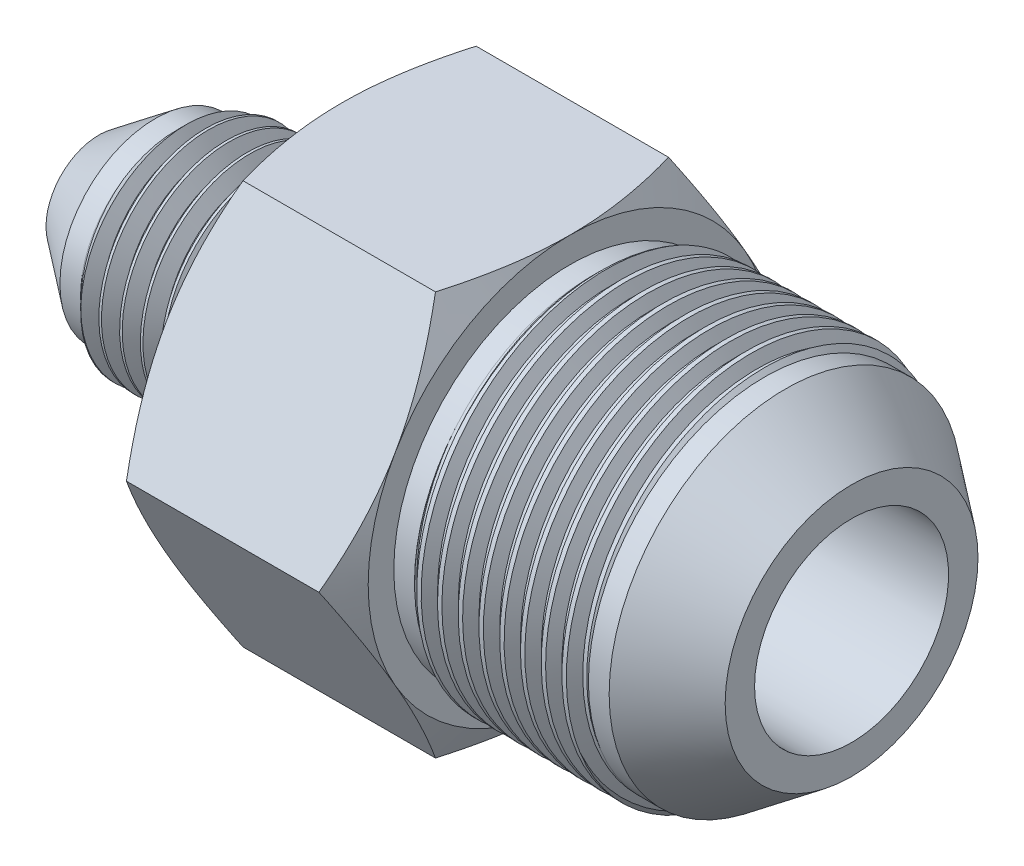
SolidWorks part; units mm, degrees
ref_plane "Front" through (0, 0, 0) normal (0, 0, 1) x (1, 0, 0)
ref_plane "Top" through (0, 0, 0) normal (0, 1, 0) x (1, 0, 0)
ref_plane "Right" through (0, 0, 0) normal (1, 0, 0) x (0, 0, -1)
sketch "Sketch1" plane through (0, 0, 0) normal (0, 0, 1) x (1, 0, 0)
  line L0 (-19.2, 5.5562) -> (-19.2, -5.5562) construction
  line L1 (19.2, 9.525) -> (19.2, -9.525) construction
  line L2 (-19.2, 0) -> (19.2, 0)
  line L4 (-19.2, 0) -> (-19.2, 5.5562)
  line L5 (4.8375, 9.525) -> (19.2, 9.525)
  line L6 (19.2, 0) -> (19.2, 9.525)
  line L7 (-19.2, 2.2) -> (-19.2, -2.2) construction
  line L8 (-6.8219, 6.3182) -> (-6.8219, -6.3182) construction
  line L9 (4.8375, 6.3182) -> (4.8375, -6.3182) construction
  line L10 (19.2, 4.95) -> (19.2, -4.95)
  point P4 (4.8375, 0)
  point P20 (19.2, 0)
  dimension "Thread Diameter 1" = 19.05
  dimension "Length" = 38.4
  dimension "L1" = 14.3625
  dimension "Thread Diameter 2" = 11.1125
  dimension "ID2" = 4.4
  dimension "D2" = 12.6365
  dimension "L2" = 12.3781
  dimension "ID1" = 9.9
sketch "Sketch2" plane through (0, 0, 0) normal (1, 0, 0) x (0, 0, -1)
  line L1 (-5.9467, 10.3) -> (-11.8934, 0) construction
  line L2 (-11.8934, 0) -> (-5.9467, -10.3) construction
  line L3 (-5.9467, -10.3) -> (5.9467, -10.3) construction
  line L4 (5.9467, -10.3) -> (11.8934, 0) construction
  line L5 (11.8934, 0) -> (5.9467, 10.3) construction
  line L6 (5.9467, 10.3) -> (-5.9467, 10.3) construction
  circle A0 centre (0, 0) radius 6.35 construction
  circle A1 centre (0, 0) radius 10.3 construction
  circle A2 centre (0, 0) radius 3.175 construction
  dimension "For Tube OD 1" = 12.7
  dimension "For Tube OD 2" = 6.35
  dimension "Hex" = 20.6
sketch "Sketch3" plane through (0, 0, 0) normal (0, 0, 1) x (1, 0, 0)
  line L0 (6.4272, 9.525) -> (4.8375, 9.525)
  line L2 (4.8375, 8.9937) -> (4.8375, 9.525)
  line L7 (19.2, 9.525) -> (14.2348, 9.525)
  line L8 (-8.5676, 5.5563) -> (-7.8802, 4.8688)
  line L10 (19.2, 0) -> (19.2, 9.525)
  line L12 (4.8375, 9.525) -> (19.2, 9.525)
  line L16 (14.2348, 9.525) -> (14.7661, 8.9937)
  line L17 (4.8375, 9.525) -> (4.8375, 10.3)
  line L18 (-14.5761, 5.5562) -> (-8.5676, 5.5563)
  line L19 (4.8375, 10.3) -> (-6.8219, 10.3)
  line L20 (-6.8219, 10.3) -> (-6.8219, 5.5562)
  line L21 (14.7661, 8.9937) -> (15.8244, 8.9937)
  line L22 (-7.8802, 4.8688) -> (-6.8219, 4.8688)
  line L24 (-19.1339, 5.6708) -> (-19.663, 4.7543)
  line L25 (-19.663, 4.7543) -> (-20.1922, 5.6708)
  line L26 (-20.1922, 5.6708) -> (-19.1339, 5.6708)
  line L27 (-19.663, 4.7543) -> (-19.663, 4.8688)
  line L28 (-19.663, 5.6708) -> (-19.663, 5.5562)
  line L29 (-19.5969, 4.8688) -> (-19.7292, 4.8688)
  line L30 (-19.2, 5.5562) -> (-20.126, 5.5562)
  line L31 (-19.1669, 5.6135) -> (-20.1591, 5.6135)
  line L32 (-6.8219, 4.8688) -> (-6.8219, 5.5562)
  line L33 (20.1471, 9.7176) -> (19.618, 8.8011)
  line L34 (19.618, 8.8011) -> (19.0888, 9.7176)
  line L35 (19.0888, 9.7176) -> (20.1471, 9.7176)
  line L36 (19.618, 8.8011) -> (19.618, 8.9937)
  line L37 (19.618, 9.7176) -> (19.618, 9.525)
  line L38 (19.7292, 8.9937) -> (19.5068, 8.9937)
  line L39 (20.0359, 9.525) -> (19.2, 9.525)
  line L40 (20.0915, 9.6213) -> (19.1444, 9.6213)
  line L41 (15.8244, 8.9937) -> (19.2, 6.45)
  line L42 (19.2, 6.45) -> (19.2, 9.525)
  line L43 (5.8958, 8.9937) -> (4.8375, 8.9937)
  line L44 (6.4272, 9.525) -> (5.8958, 8.9937)
  line L45 (19.2, 0) -> (19.2, 9.525) construction
  line L46 (0, -10.3) -> (0, 10.3) construction
  line L47 (-19.2, 2.7) -> (-16.3218, 4.8688)
  line L48 (-19.2, 0) -> (-19.2, 5.5562) construction
  line L49 (-16.3218, 4.8688) -> (-15.2635, 4.8688)
  line L50 (-15.2635, 4.8688) -> (-14.5761, 5.5562)
  line L51 (19.2, 0) -> (4.8375, 0)
  line L52 (4.8375, 0) -> (-6.8219, 0)
  line L53 (-6.8219, 6.3182) -> (-6.8219, -6.3182) construction
  line L54 (-6.8219, 0) -> (-19.2, 0)
  line L55 (-19.2, 5.5562) -> (-19.2, -5.5562) construction
  line L56 (-19.2, 0) -> (-19.2, 2.7)
  point P14 (-19.2, 5.5562)
  point P43 (-19.663, 4.8688)
  point P46 (-19.663, 5.5562)
  point P49 (-19.663, 5.6135)
  point P57 (19.618, 8.9937)
  point P59 (19.618, 9.525)
  point P63 (19.618, 9.6213)
  point P86 (0, 10.3)
  dimension "Pitch2" = 1.0583
  dimension "D3" = 0.1323
  dimension "Pitch1" = 1.0583
  dimension "D4" = 0.2224
  dimension "Flare Angle" = 37
  dimension "D6" = 45
  dimension "Flare Angle 2" = 37
  dimension "D1" = 45
  dimension "Thread Length 1" = 13.3042
  dimension "Thread Length 2" = 11.3198
  dimension "D5" = 1.5
sketch "Sketch6" plane through (0, 0, 0) normal (0, 0, 1) x (1, 0, 0)
  line L0 (14.2348, 9.525) -> (14.7661, 8.9937) construction
  line L2 (14.7661, 8.9937) -> (15.8244, 8.9937) construction
  line L7 (15.8244, 8.9937) -> (19.2, 6.45) construction
  line L16 (-19.2, 0) -> (19.2, 0) construction
  line L21 (14.2348, 9.525) -> (14.7661, 8.9937)
  line L25 (14.7661, 8.9937) -> (15.8244, 8.9937)
  line L26 (15.8244, 8.9937) -> (19.2, 6.45)
  line L27 (-19.2, 0) -> (19.2, 0)
  line L28 (4.8375, 6.3182) -> (4.8375, -6.3182) construction
  line L29 (4.8375, 10.3) -> (-6.8219, 10.3) construction
  line L30 (-6.8219, 6.3182) -> (-6.8219, -6.3182) construction
  line L31 (-19.2, 2.7) -> (-16.3218, 4.8688) construction
  line L32 (-16.3218, 4.8688) -> (-15.2635, 4.8688) construction
  line L33 (-15.2635, 4.8688) -> (-14.5761, 5.5562) construction
  line L34 (-14.5761, 5.5562) -> (-8.5676, 5.5563) construction
  line L35 (-8.5676, 5.5563) -> (-7.8802, 4.8688) construction
  line L36 (-7.8802, 4.8688) -> (-6.8219, 4.8688) construction
  line L37 (5.8958, 8.9937) -> (4.8375, 8.9937) construction
  line L38 (6.4272, 9.525) -> (5.8958, 8.9937) construction
  line L39 (4.8375, 10.3) -> (4.8375, 8.9937)
  line L40 (4.8375, 10.3) -> (-6.8219, 10.3)
  line L41 (-6.8219, 10.3) -> (-6.8219, 4.8688)
  line L42 (-19.2, 2.7) -> (-16.3218, 4.8688)
  line L43 (-16.3218, 4.8688) -> (-15.2635, 4.8688)
  line L44 (-15.2635, 4.8688) -> (-14.5761, 5.5562)
  line L45 (-14.5761, 5.5562) -> (-8.5676, 5.5563)
  line L46 (-8.5676, 5.5563) -> (-7.8802, 4.8688)
  line L47 (-7.8802, 4.8688) -> (-6.8219, 4.8688)
  line L48 (5.8958, 8.9937) -> (4.8375, 8.9937)
  line L49 (6.4272, 9.525) -> (5.8958, 8.9937)
  line L50 (19.2, 6.45) -> (19.2, 0)
  line L51 (14.2348, 9.525) -> (6.4272, 9.525)
  line L52 (-19.2, 2.7) -> (-19.2, 0)
revolve "Revolve3" add sketch "Sketch6" angle 360 about L27
sketch "Sketch14" plane through (19.2, 0, 0) normal (-1, 0, 0) x (0, 0, 1)
  circle A2 centre (0, 0) radius 9.525
sketch "Sketch15" plane through (0, 0, 0) normal (0, 0, 1) x (1, 0, 0)
  line L1 (20.0915, 9.6213) -> (19.7292, 8.9937)
  line L2 (19.7292, 8.9937) -> (19.5068, 8.9937)
  line L3 (19.5068, 8.9937) -> (19.1444, 9.6213)
  line L4 (19.1444, 9.6213) -> (20.0915, 9.6213)
ref_plane "Plane1" through (-6.8219, 0, 0) normal (1, 0, 0) x (0, 0, -1)
sketch "Sketch12" plane through (-6.8219, 0, 0) normal (1, 0, 0) x (0, 0, -1)
  line L0 (5.9467, 10.3) -> (-5.9467, 10.3) construction
  line L1 (-5.9467, 10.3) -> (-11.8934, 0) construction
  line L2 (-11.8934, 0) -> (-5.9467, -10.3) construction
  line L3 (-5.9467, -10.3) -> (5.9467, -10.3) construction
  line L4 (5.9467, -10.3) -> (11.8934, 0) construction
  line L5 (11.8934, 0) -> (5.9467, 10.3) construction
  line L7 (5.9467, 10.3) -> (-5.9467, 10.3)
  line L8 (-5.9467, 10.3) -> (-11.8934, 0)
  line L9 (-11.8934, 0) -> (-5.9467, -10.3)
  line L10 (-5.9467, -10.3) -> (5.9467, -10.3)
  line L11 (5.9467, -10.3) -> (11.8934, 0)
  line L12 (11.8934, 0) -> (5.9467, 10.3)
extrude "Extrude1" add sketch "Sketch12" along normal up to vertex (11.6594 mm away) up to point (4.8375, 6.3182, 0)
sketch "Sketch7" plane through (0, 0, 0) normal (0, 0, 1) x (1, 0, 0)
  line L0 (-19.2, 2.2) -> (-19.2, 0)
  line L1 (-19.2, 0) -> (19.2, 0)
  line L3 (-19.2, 2.2) -> (-1, 2.2)
  line L4 (19.2, 4.95) -> (0.5, 4.95)
  line L5 (19.2, 4.95) -> (19.2, 0)
  line L7 (-1, 2.2) -> (0.5, 4.95)
  dimension "D1" = 1
sketch "Sketch22" plane through (-6.8219, 0, 0) normal (-1, 0, 0) x (0, 0, 1)
  circle A0 centre (0, 0) radius 10.3 construction
  circle A1 centre (0, 0) radius 10.3
extrude "Cut-Extrude1" cut sketch "Sketch22" against normal through all draft 60 flip side to cut
sketch "Sketch23" plane through (4.8375, 0, 0) normal (1, 0, 0) x (0, 0, -1)
  circle A0 centre (0, 0) radius 10.3 construction
  circle A1 centre (0, 0) radius 10.3
extrude "Cut-Extrude2" cut sketch "Sketch23" against normal through all draft 60 and the other way through all flip side to cut
revolve "Cut-Revolve5" cut sketch "Sketch7" angle 360 about L1
sketch "Sketch20" plane through (-19.2, 0, 0) normal (1, 0, 0) x (0, 0, -1)
  circle A1 centre (0, 0) radius 5.5562
ref_plane "Plane2" through (-19.2, 0, 0) normal (1, 0, 0) x (0, 0, -1)
curve "Helix/Spiral2" pitch 1.0583 height 11.8198 radius 5.5562 centre (-19.2, 0, 0) axis (1, 0, 0) start towards (0, 1, 0) parameters "Pitch"=1.0583
sketch "Sketch21" plane through (0, 0, 0) normal (0, 0, 1) x (1, 0, 0)
  line L0 (-19.1669, 5.6135) -> (-19.5969, 4.8688)
  line L1 (-19.5969, 4.8688) -> (-19.7292, 4.8688)
  line L2 (-19.7292, 4.8688) -> (-20.1591, 5.6135)
  line L3 (-20.1591, 5.6135) -> (-19.1669, 5.6135)
curve "Helix/Spiral1" pitch 1.0583 height 14.0542 radius 9.525 centre (19.2, 0, 0) axis (-1, 0, 0) start towards (0, 1, 0) parameters "Pitch"=1.0583
sweep "Cut-Sweep1" cut profiles "Sketch15" path "Helix/Spiral1" align with end faces yes
sweep "Cut-Sweep2" cut profiles "Sketch21" path "Helix/Spiral2"
equation "\"D3@Helix/Spiral1\"=\"Thread Length 1@Sketch3\" +.75"
equation "\"D3@Helix/Spiral2\"=\"Thread Length 2@Sketch3\" + .5"
equation "\"Pitch@Helix/Spiral2\"=\"Pitch2@Sketch3\""
equation "\"Pitch@Helix/Spiral1\"=\"Pitch1@Sketch3\""
equation "\"D3@Sketch3\"=\"Pitch2@Sketch3\"/8"
equation "\"L2@Sketch1\"=(\"Length@Sketch1\"+\"Thread Diameter 2@Sketch1\")*.25"
equation "\"L1@Sketch1\"=(\"Length@Sketch1\"+\"Thread Diameter 1@Sketch1\")*.25"
equation "\"D2@Sketch7\"=\"D1@Sketch7\"/2"
